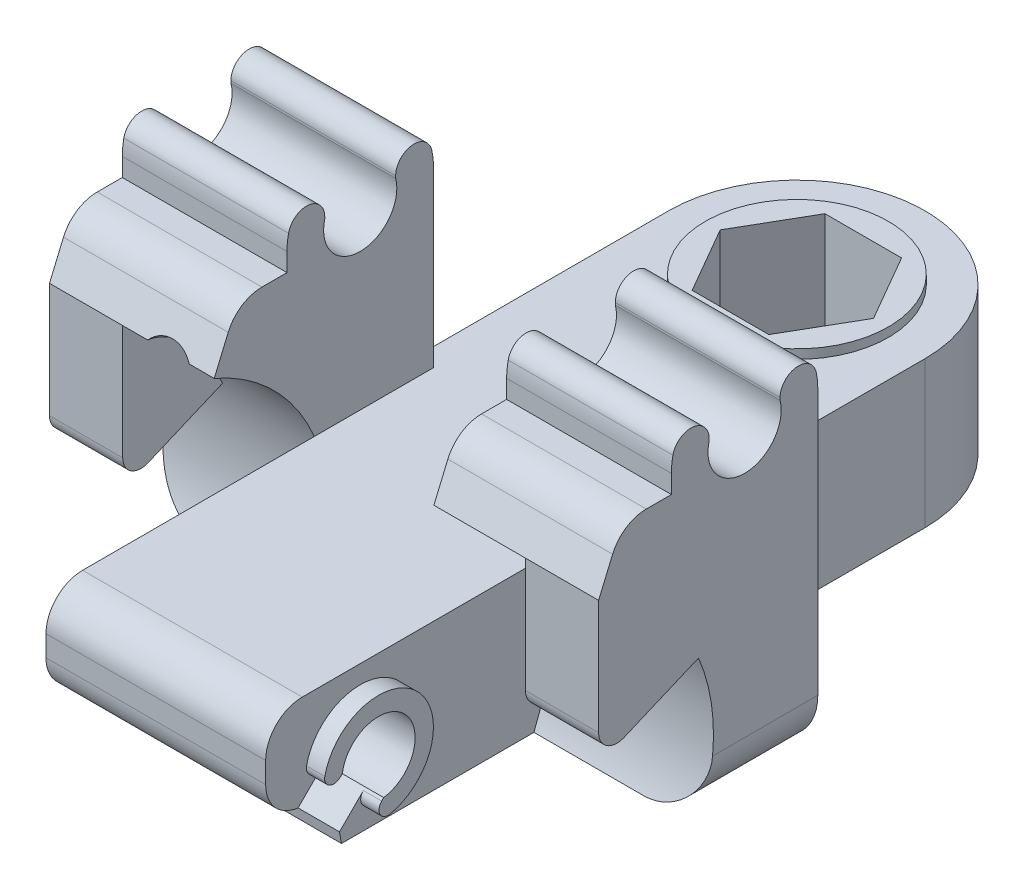
SolidWorks part; units mm, degrees
ref_plane "Front Plane" through (0, 0, 0) normal (0, 0, 1) x (1, 0, 0)
ref_plane "Top Plane" through (0, 0, 0) normal (0, 1, 0) x (1, 0, 0)
ref_plane "Right Plane" through (0, 0, 0) normal (1, 0, 0) x (0, 0, -1)
sketch "Sketch3" plane through (0, 0, 0) normal (1, 0, 0) x (0, 0, -1)
  line L0 (0.2828, -1.9799) -> (-1.9799, 0.2828)
  line L1 (0.2828, -1.9799) -> (-1.1314, -3.3941)
  line L2 (-1.1314, -3.3941) -> (-0.8188, -5.1668)
  line L3 (-0.8188, -5.1668) -> (-4.7772, -9.1252)
  line L4 (-1.9799, 0.2828) -> (-3.3941, -1.1314)
  line L5 (-3.3941, -1.1314) -> (-5.1668, -0.8188)
  line L6 (-5.1668, -0.8188) -> (-9.1252, -4.7772)
  line L7 (-0.8485, -0.8485) -> (0, 0) construction
  line L8 (0, 0) -> (-2, 0) construction
  line L9 (-1.9799, 0.2828) -> (-5.1668, -0.8188) construction
  line L10 (-0.8188, -5.1668) -> (0.2828, -1.9799) construction
  circle A0 centre (0, 0) radius 2
  circle A1 centre (0, 0) radius 9.8 construction
  circle A2 centre (0, 0) radius 10.3 construction
  circle A3 centre (0, 0) radius 10.3
  dimension "D1" = 4
  dimension "D2" = 19.6
  dimension "D4" = 0.5
  dimension "D5" = 2
  dimension "D7" = 3.2
  dimension "D6" = 1.8
  dimension "D8" = 45
  dimension "D9" = 125
extrude "Boss-Extrude1" add sketch "Sketch3" along normal mid plane 12 contours A3 L6 L5 L4 A0 L1 L2 L3 | A3 region at (0, -1.5013, -1.731)
sketch "Sketch5" plane through (0, 0, 0) normal (1, 0, 0) x (0, 0, -1)
  line L0 (0, 10.3) -> (29.856, 10.3)
  line L1 (29.856, 10.3) -> (29.856, -10.3)
  line L2 (29.856, -10.3) -> (0, -10.3)
  arc A0 (-4.7772, -9.1252) -> (-9.1252, -4.7772) centre (0, 0) ccw construction
  arc A1 (0, -10.3) -> (0, 10.3) centre (0, 0) ccw
  dimension "D1" = 29.856
extrude "Boss-Extrude2" add sketch "Sketch5" along normal mid plane 14
sketch "Sketch6" plane through (0, 10.3, 0) normal (0, 1, 0) x (1, 0, 0)
  line L0 (7, 29.856) -> (-7, 29.856) construction
  circle A0 centre (0, 29.856) radius 7
extrude "Boss-Extrude3" add sketch "Sketch6" against normal up to surface (20.6 mm away) up to face at (0, -10.3, -9.952)
sketch "Sketch7" plane through (0, 0, 0) normal (0, 1, 0) x (1, 0, 0)
  circle A0 centre (0, 29.856) radius 4.5
  dimension "D1" = 9
extrude "Boss-Extrude4" add sketch "Sketch7" along normal blind 8 and the other way blind 8
sketch "Sketch8" plane through (0, 10.3, 0) normal (0, 1, 0) x (1, 0, 0)
  line L0 (6, -10.3) -> (6, 0) construction
  line L1 (-6, 0) -> (-6, -10.3) construction
  line L3 (7, 0) -> (7, 29.856) construction
  line L4 (-7, 29.856) -> (-7, 0) construction
  line L5 (-7, 0) -> (-6, 0) construction
  line L6 (6, 0) -> (7, 0) construction
  line L7 (6, -10.3) -> (6, 0)
  line L8 (-6, 0) -> (-6, -10.3)
  line L9 (-6, -10.3) -> (6, -10.3)
  line L10 (7, 0) -> (7, 29.856)
  line L11 (-7, 29.856) -> (-7, 0)
  line L12 (-7, 0) -> (-6, 0)
  line L13 (6, 0) -> (7, 0)
  arc A0 (7, 29.856) -> (-7, 29.856) centre (0, 29.856) ccw construction
  arc A1 (7, 29.856) -> (-7, 29.856) centre (0, 29.856) ccw
  line M10 (7, 0) -> (7, 29.856)
  arc M11 (7, 29.856) -> (-7, 29.856) centre (0, 29.856) ccw
  line M12 (-7, 29.856) -> (-7, 0)
  line M13 (-7, 0) -> (-6, 0)
  line M14 (-6, 0) -> (6, 0)
  line M15 (6, 0) -> (7, 0)
extrude "Cut-Extrude2" cut sketch "Sketch8" against normal offset from surface (6.3 mm away) 4 contours M15 M10 M11 M12 M13 M14 | L8 L9 L7 M14 region at (0, 10.3, 5.15) region at (0, 10.3, -17.7114) up to plane "Top Plane"
sketch "Sketch9" plane through (0, -10.3, 0) normal (0, -1, 0) x (1, 0, 0)
  line L7 (6, 0) -> (6, 10.3)
  line L8 (7, 0) -> (6, 0)
  line L9 (7, -29.856) -> (7, 0)
  line L10 (-7, 0) -> (-7, -29.856)
  line L11 (-6, 0) -> (-7, 0)
  line L12 (-6, 10.3) -> (-6, 0)
  line L13 (6, 10.3) -> (-6, 10.3)
  line L14 (6, 0) -> (6, 10.3)
  line L15 (7, 0) -> (6, 0)
  line L16 (7, -29.856) -> (7, 0)
  line L17 (-7, 0) -> (-7, -29.856)
  line L18 (-6, 0) -> (-7, 0)
  line L19 (-6, 10.3) -> (-6, 0)
  line L20 (6, 10.3) -> (-6, 10.3)
  arc A1 (-7, -29.856) -> (7, -29.856) centre (0, -29.856) ccw
  arc A2 (-7, -29.856) -> (7, -29.856) centre (0, -29.856) ccw
  line M10 (-7, 0) -> (-7, -29.856)
  arc M11 (-7, -29.856) -> (7, -29.856) centre (0, -29.856) ccw
  line M12 (7, -29.856) -> (7, 0)
  line M13 (7, 0) -> (6, 0)
  line M14 (6, 0) -> (-6, 0)
  line M15 (-6, 0) -> (-7, 0)
  dimension "D1" = 0
extrude "Cut-Extrude4" cut sketch "Sketch9" against normal offset from surface (6.3 mm away) 4 contours M15 M10 M11 M12 M13 M14 | L14 L20 L19 M14 region at (0, -10.3, 5.15) region at (0, -10.3, -17.7114) up to plane "Top Plane"
sketch "Sketch24" plane through (-6, 0, 0) normal (-1, 0, 0) x (0, 0, 1)
  line L0 (1.9799, 0.2828) -> (2.9258, -0.6631)
  line L1 (1.9799, 0.2828) -> (3.3941, -1.1314) construction
  line L2 (-0.2828, -1.9799) -> (0.6631, -2.9258)
  line L3 (-0.2828, -1.9799) -> (1.1314, -3.3941) construction
  arc A0 (1.9799, 0.2828) -> (-0.2828, -1.9799) centre (0, 0) ccw construction
  arc A1 (1.9799, 0.2828) -> (-0.2828, -1.9799) centre (0, 0) ccw
  circle A2 centre (0, 0) radius 3
  line M5 (1.1314, -3.3941) -> (-0.2828, -1.9799)
  arc M6 (-0.2828, -1.9799) -> (1.9799, 0.2828) centre (0, 0) cw
  line M7 (1.9799, 0.2828) -> (3.3941, -1.1314)
  dimension "D1" = 6
extrude "Boss-Extrude6" add sketch "Sketch24" along normal blind 1 contours A2 M7 M5 M6 region at (-6, 1.4742, -1.4742)
fillet "Fillet3" radius 0.5 2 edges at (-6.5, -2.9258, 0.6631) (-6.5, -0.6631, 2.9258)
mirror "Mirror1" about plane through (0, 0, 0) normal (1, 0, 0) of "Fillet3", "Boss-Extrude6"
sketch "Sketch10" plane through (0, 0, 0) normal (1, 0, 0) x (0, 0, -1)
  line L3 (9.4916, -4) -> (29.856, -4)
  line L4 (29.856, -4) -> (29.856, 4)
  line L5 (29.856, 4) -> (9.4916, 4)
  line L10 (8, 12.5) -> (8, 17.5) construction
  line L11 (8, 17.5) -> (16, 17.5) construction
  line L12 (16, 17.5) -> (16, 4) construction
  line L13 (5.3059, 12.5) -> (8, 12.5)
  line L14 (0, 0) -> (4.0245, 9.4812) construction
  line L15 (4.0245, 9.4812) -> (5.3059, 12.5)
  line L16 (29.856, 4) -> (9.4916, 4) construction
  line L17 (16, 4) -> (9.4916, 4)
  line L18 (8, 13.5) -> (16, 13.5) construction
  line L19 (26, 14) -> (26, 4) construction
  line L20 (29.856, -4) -> (9.4916, -4) construction
  line L21 (10.0635, 14) -> (13.9365, 14) construction
  line L22 (13.9365, 14) -> (13.9365, 17)
  line L23 (10.0635, 17) -> (10.0635, 14)
  line L24 (8, 13.5) -> (8, 12.5)
  line L25 (16, 13.5) -> (16, 4)
  line L26 (16, -4) -> (9.4916, -4)
  line L27 (16, 4) -> (16, -4)
  arc A0 (10.0635, 14) -> (13.9365, 14) centre (12, 13.5) ccw
  arc A1 (9.4916, -4) -> (9.4916, 4) centre (0, 0) ccw
  arc A2 (9.4916, 4) -> (4.0245, 9.4812) centre (0, 0) ccw
  arc A3 (16, 13.5) -> (13.9365, 17) centre (12, 13.5) ccw
  arc A4 (10.0635, 17) -> (8, 13.5) centre (12, 13.5) ccw
  arc A5 (9.4916, -4) -> (9.4916, 4) centre (0, 0) ccw construction
  arc A6 (9.4916, -4) -> (9.4916, 4) centre (0, 0) ccw
  dimension "D8" = 4
  dimension "D9" = 2
  dimension "D10" = 2.5
  dimension "D2" = 67
  dimension "D3" = 10
  dimension "D4" = 13.5
  dimension "D5" = 5
  dimension "D6" = 12
  dimension "D7" = 5
  dimension "D1" = 0
extrude "Boss-Extrude5" add sketch "Sketch10" along normal mid plane 30 contours A6 L26 L27 L17 | L23 A4 L24 L13 L15 A2 L17 L25 A3 L22 A0 region at (0, 0, -13.0126) region at (0, 9.4691, -11.1839)
ref_plane "Plane1" through (6, 0, 0) normal (1, 0, 0) x (0, 0, -1)
ref_plane "Plane2" through (-6, 0, 0) normal (1, 0, 0) x (0, 0, -1)
sketch "Sketch13" plane through (-6, 0, 0) normal (1, 0, 0) x (0, 0, -1)
  line L0 (0, 5) -> (36.856, 5)
  line L2 (36.856, 4) -> (36.856, 5) construction
  circle A0 centre (0, 0) radius 5 construction
  dimension "D1" = 10
ref_plane "Plane3" through (0, 0, 0) normal (0, 0, 1) x (1, 0, 0)
ref_plane "Plane4" [suppressed] through (0, 0, -32.856) normal (0, 0, -1) x (-1, 0, 0)
ref_plane "Plane5" [suppressed] through (-3, 0, 0) normal (-1, 0, 0) x (0, 0, 1)
sketch "Sketch18" [suppressed] plane through (0, 0, -32.856) normal (0, 0, -1) x (-1, 0, 0)
  line L0 (0, 29) -> (0, 16) construction
  line L2 (3, 29) -> (-3, 29) construction
  circle A0 centre (0, 16) radius 1.9
  dimension "D2" = 3.8
  dimension "D1" = 13
extrude "Cut-Extrude5" [suppressed] cut sketch "Sketch18" against normal blind 1
sketch "Sketch20" plane through (0, 4, 0) normal (0, 1, 0) x (1, 0, 0)
  line L0 (0, 25.356) -> (0, 0) construction
  line L2 (-6, -16) -> (6, -16)
  line L3 (-6, -16) -> (-6, 16)
  line L4 (-6, 16) -> (6, 16)
  line L5 (6, -16) -> (6, 16)
  line L6 (-6, -16) -> (6, 16) construction
  line L7 (-6, 16) -> (6, -16) construction
  line L8 (-7, 16) -> (7, 16) construction
  dimension "D1" = 12
extrude "Cut-Extrude7" cut sketch "Sketch20" along normal through all
sketch "Sketch32" plane through (6, 0, 0) normal (1, 0, 0) x (0, 0, -1)
  line L0 (-5.1668, -0.8188) -> (-5.1668, 4)
  line L1 (9.4916, 4) -> (-9.4916, 4) construction
  line L9 (-3.3941, -1.1314) -> (-2.0905, 0.1722)
  line L10 (0.1722, -2.0905) -> (-1.1314, -3.3941)
  line L11 (-1.1314, -3.3941) -> (-1.0245, -4)
  line L12 (-1.0245, -4) -> (9.4916, -4)
  line L13 (9.4916, 4) -> (-9.4916, 4)
  line L14 (-8.348, -4) -> (-5.1668, -0.8188)
  line L15 (-5.1668, -0.8188) -> (-3.3941, -1.1314)
  line L16 (-3.3941, -1.1314) -> (-2.0905, 0.1722)
  line L17 (0.1722, -2.0905) -> (-1.1314, -3.3941)
  line L18 (-1.1314, -3.3941) -> (-1.0245, -4)
  line L19 (-1.0245, -4) -> (9.4916, -4)
  line L20 (9.4916, 4) -> (-9.4916, 4)
  line L21 (-8.348, -4) -> (-5.1668, -0.8188)
  line L22 (-5.1668, -0.8188) -> (-3.3941, -1.1314)
  line L24 (-9.4916, -4) -> (-8.348, -4)
  line L25 (-9.4916, -4) -> (-8.348, -4)
  arc A5 (-2.9329, 0.6309) -> (-2.0905, 0.1722) centre (-2.4441, 0.5258) ccw
  arc A6 (0.6309, -2.9329) -> (-2.9329, 0.6309) centre (0, 0) ccw
  arc A7 (0.1722, -2.0905) -> (0.6309, -2.9329) centre (0.5258, -2.4441) ccw
  arc A8 (9.4916, -4) -> (9.4916, 4) centre (0, 0) ccw
  arc A9 (-9.4916, 4) -> (-9.4916, -4) centre (0, 0) ccw
  arc A10 (-2.9329, 0.6309) -> (-2.0905, 0.1722) centre (-2.4441, 0.5258) ccw
  arc A11 (0.6309, -2.9329) -> (-2.9329, 0.6309) centre (0, 0) ccw
  arc A12 (0.1722, -2.0905) -> (0.6309, -2.9329) centre (0.5258, -2.4441) ccw
  arc A13 (9.4916, -4) -> (9.4916, 4) centre (0, 0) ccw
  arc A14 (-9.4916, 4) -> (-9.4916, -4) centre (0, 0) ccw
  line M21 (9.4916, 4) -> (-9.4916, 4)
  arc M22 (-9.4916, 4) -> (-9.4916, -4) centre (0, 0) ccw
  line M23 (-8.348, -4) -> (-5.1668, -0.8188)
  dimension "D1" = 0
extrude "Cut-Extrude9" cut sketch "Sketch32" against normal blind 25 contours L0 M23 M21 M22 region at (6, 0.439, 7.8127)
fillet "Fillet1" radius 2 2 edges at (0, 4, 5.1668) (0, -0.8188, 5.1668)
fillet "Fillet2" radius 1 4 edges at (-10.5, 17, -13.9365) (-10.5, 17, -10.0635) (10.5, 17, -10.0635) (10.5, 17, -13.9365)
sketch "Sketch23" plane through (0, 4, 0) normal (0, 1, 0) x (1, 0, 0)
  line L0 (-7, 29.856) -> (7, 29.856) construction
  line L1 (4.1881, 29.856) -> (2.094, 33.483)
  line L2 (2.094, 33.483) -> (-2.094, 33.483)
  line L3 (-2.094, 33.483) -> (-4.1881, 29.856)
  line L4 (-4.1881, 29.856) -> (-2.094, 26.229)
  line L5 (-2.094, 26.229) -> (2.094, 26.229)
  line L6 (2.094, 26.229) -> (4.1881, 29.856)
  line L7 (-7, 16) -> (-7, 29.856) construction
  circle A0 centre (0, 29.856) radius 3.627 construction
  dimension "D1" = 7.254
extrude "Cut-Extrude8" cut sketch "Sketch23" against normal through all
sketch "Sketch25" plane through (15, 0, 0) normal (1, 0, 0) x (0, 0, -1)
  line L0 (10.0635, 13) -> (13.9365, 13)
  arc A0 (10.0635, 14) -> (13.9365, 14) centre (12, 13.5) ccw construction
  arc A1 (10.0635, 14) -> (13.9365, 14) centre (12, 13.5) ccw
  arc M14 (13.9365, 14) -> (10.0635, 14) centre (12, 13.5) cw
  dimension "D1" = 1.5
extrude "Boss-Extrude7" [suppressed] add sketch "Sketch25" against normal blind 1 contours L0 M14
fillet "Fillet4" [suppressed] radius 0.5
mirror "Mirror2" [suppressed] about plane through (0, 0, 0) normal (1, 0, 0)
fillet "Fillet5" radius 3 2 edges at (15, -4, -12.7458) (-15, -4, -12.7458)
fillet "Fillet7" radius 2 2 edges at (-10.5, 12.5, -5.3059) (10.5, 12.5, -5.3059)
ref_plane "Plane6" through (-8.5, 0, 0) normal (-1, 0, 0) x (0, 0, 1)
sketch "Sketch27" plane through (-8.5, 0, 0) normal (-1, 0, 0) x (0, 0, 1)
  line L0 (0, 8.5) -> (-25.4214, 8.5)
  circle A0 centre (0, 0) radius 8.5 construction
  dimension "D1" = 17
sweep "Cut-Sweep1" cut path "Sketch27" circular profile diameter 3 parameters "D3"=3
sketch "Sketch28" plane through (15, 0, 0) normal (1, 0, 0) x (0, 0, -1)
  line L0 (0, 0) -> (9.4812, 4.0245) construction
  line L1 (9.4812, 4.0245) -> (4.0245, 1.7083)
  line L2 (0, 0) -> (0, 8.2854) construction
  line L3 (4.0245, 1.7083) -> (4.0245, 9.4812)
  arc A0 (10.2513, -1) -> (4.0245, 9.4812) centre (0, 0) ccw construction
  arc A1 (10.2513, -1) -> (4.0245, 9.4812) centre (0, 0) ccw
  arc M6 (4.0245, 9.4812) -> (10.2513, -1) centre (0, 0) cw
  dimension "D1" = 67
extrude "Boss-Extrude8" add sketch "Sketch28" against normal blind 4 contours L3 L1 M6 region at (15, 5.3648, -6.0173)
fillet "Fillet8" radius 1 1 edges at (13, 1.7083, -4.0245)
mirror "Mirror3" about plane through (0, 0, 0) normal (1, 0, 0) of "Fillet8", "Boss-Extrude8"
sketch "Sketch33" plane through (0, 4, 0) normal (0, 1, 0) x (1, 0, 0)
  line L0 (4.1881, 29.856) -> (2.094, 33.483) construction
  line L1 (2.094, 26.229) -> (4.1881, 29.856) construction
  line L2 (-2.094, 26.229) -> (2.094, 26.229) construction
  line L3 (-4.1881, 29.856) -> (-2.094, 26.229) construction
  line L4 (-2.094, 33.483) -> (-4.1881, 29.856) construction
  line L5 (2.094, 33.483) -> (-2.094, 33.483) construction
  line L6 (4.1881, 29.856) -> (2.094, 33.483)
  line L7 (2.094, 26.229) -> (4.1881, 29.856)
  line L8 (-2.094, 26.229) -> (2.094, 26.229)
  line L9 (-4.1881, 29.856) -> (-2.094, 26.229)
  line L10 (-2.094, 33.483) -> (-4.1881, 29.856)
  line L11 (2.094, 33.483) -> (-2.094, 33.483)
  arc A0 (7, 29.856) -> (-7, 29.856) centre (0, 29.856) ccw construction
  arc A1 (7, 29.856) -> (-7, 29.856) centre (0, 29.856) ccw
  circle A2 centre (0, 29.856) radius 5
  line M8 (4.1881, 29.856) -> (2.094, 26.229)
  line M9 (2.094, 26.229) -> (-2.094, 26.229)
  line M10 (-2.094, 26.229) -> (-4.1881, 29.856)
  line M11 (-4.1881, 29.856) -> (-2.094, 33.483)
  line M12 (-2.094, 33.483) -> (2.094, 33.483)
  line M13 (2.094, 33.483) -> (4.1881, 29.856)
  dimension "D1" = 10
extrude "Boss-Extrude9" add sketch "Sketch33" along normal blind 0.5 contours A2 M13 M8 M9 M10 M11 M12 region at (-4.8586, 4, -29.856)
ref_plane "Plane7" through (0, 0, 0) normal (0, -1, 0) x (-1, 0, 0)
